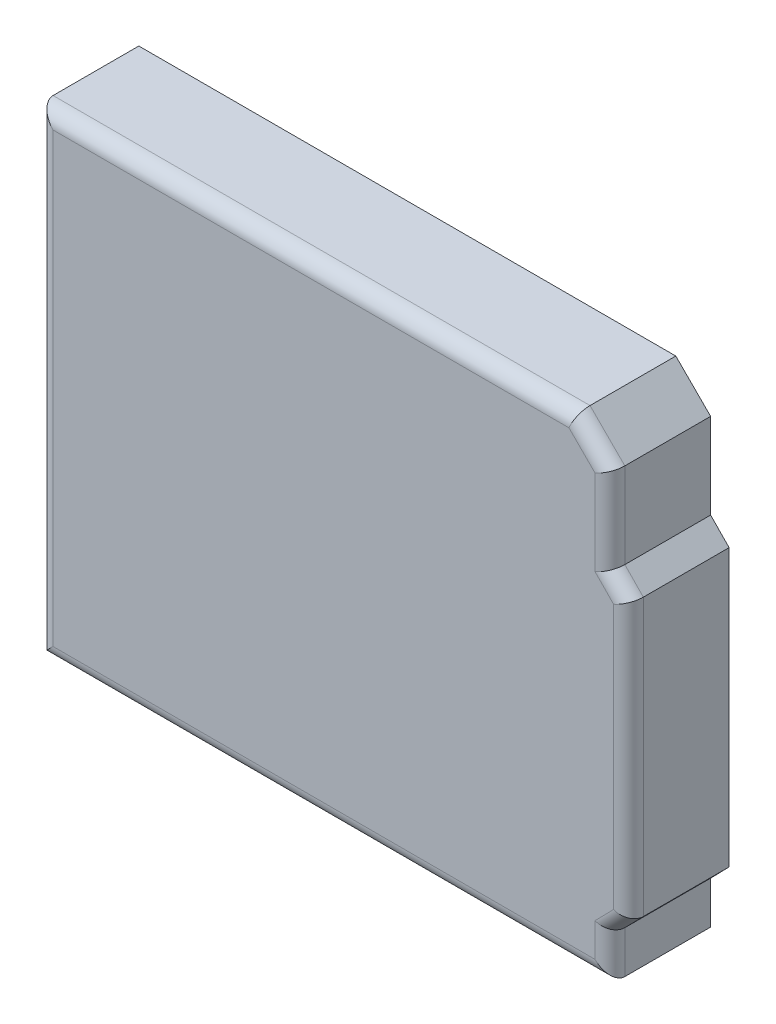
SolidWorks part; units mm, degrees
ref_plane "Front Plane" through (0, 0, 0) normal (0, 0, 1) x (1, 0, 0)
ref_plane "Top Plane" through (0, 0, 0) normal (0, 1, 0) x (1, 0, 0)
ref_plane "Right Plane" through (0, 0, 0) normal (1, 0, 0) x (0, 0, -1)
sketch "Sketch4" plane through (0, 0, 0) normal (0, 0, 1) x (1, 0, 0)
  line L25 (-58.7815, 16.139) -> (-58.7815, -3.121)
  line L26 (-58.7815, -3.121) -> (-54.0815, -3.121)
  line L27 (-54.0815, -3.121) -> (-54.0815, 16.139)
  line L28 (-54.0815, 16.139) -> (-58.7815, 16.139)
  line L29 (-54.0815, -12.7107) -> (-58.7815, -12.7107)
  line L30 (-58.7815, -12.7107) -> (-58.7815, -20.8795)
  line L31 (-58.7815, -20.8795) -> (17.8885, -20.8795)
  line L32 (17.8885, -20.8795) -> (17.8885, -15.1978)
  line L33 (17.8885, -15.1978) -> (20.3685, -12.6578)
  line L34 (20.3685, -12.6578) -> (20.3685, 24.4249)
  line L35 (20.3685, 24.4249) -> (17.8885, 26.9649)
  line L36 (17.8885, 26.9649) -> (17.8885, 38.4295)
  line L37 (17.8885, 38.4295) -> (13.2191, 43.099)
  line L38 (13.2191, 43.099) -> (-58.7815, 43.099)
  line L39 (-58.7815, 43.099) -> (-58.7815, 28.739)
  line L40 (-58.7815, 28.739) -> (-54.0815, 28.739)
  line L41 (-54.0815, 28.739) -> (-54.0815, 38.399)
  line L42 (-54.0815, 38.399) -> (13.1885, 38.399)
  line L43 (13.1885, 38.399) -> (13.1885, 25.0509)
  line L44 (13.1885, 25.0509) -> (15.6685, 22.5109)
  line L45 (15.6685, 22.5109) -> (15.6685, -10.7438)
  line L46 (15.6685, -10.7438) -> (13.1885, -13.2838)
  line L47 (13.1885, -13.2838) -> (13.1885, -16.1795)
  line L48 (13.1885, -16.1795) -> (-54.0815, -16.1795)
  line L49 (-54.0815, -16.1795) -> (-54.0815, -12.7107)
  line L51 (-58.7815, 28.739) -> (-54.0815, 28.739)
  line L52 (-58.7815, 28.739) -> (-58.7815, 16.139)
  line L53 (-58.7815, 16.139) -> (-54.0815, 16.139)
  line L54 (-54.0815, 28.739) -> (-54.0815, 16.139)
  line L55 (-58.7815, -3.121) -> (-54.0815, -3.121)
  line L56 (-58.7815, -3.121) -> (-58.7815, -12.7107)
  line L57 (-58.7815, -12.7107) -> (-54.0815, -12.7107)
  line L58 (-54.0815, -3.121) -> (-54.0815, -12.7107)
extrude "Boss-Extrude1" add sketch "Sketch4" along normal blind 13.5 contours L27 L58 L49 L48 L47 L46 L45 L44 L43 L42 L41 L54 | L48 L49 L29 L30 L31 L32 L33 L34 L35 L36 L37 L38 L39 L40 L41 L42 L43 L44 L45 L46 L47 | L54 L40 L52 L28 | L27 L28 L25 L26 | L58 L26 L56 L29 region at (-56.4315, 6.509, 0) region at (-56.4315, 22.439, 0) region at (-56.4315, -7.9158, 0) region at (-19.6238, 10.9864, 0) region at (-57.7637, 35.919, 0)
sketch "Sketch6" plane through (0, 0, 0) normal (0, 0, -1) x (-1, 0, 0)
  line L54 (53.7815, -15.8795) -> (53.7815, 38.099)
  line L55 (-12.8885, -15.8795) -> (53.7815, -15.8795)
  line L56 (-15.3685, -10.6216) -> (-12.8885, -13.1616)
  line L57 (-15.3685, 22.3887) -> (-15.3685, -10.6216)
  line L58 (-12.8885, 24.9287) -> (-15.3685, 22.3887)
  line L59 (-12.8885, 36.3585) -> (-12.8885, 24.9287)
  line L60 (53.7815, 38.099) -> (-11.148, 38.099)
  line L61 (53.7815, -15.8795) -> (53.7815, 38.099)
  line L62 (-12.8885, -15.8795) -> (53.7815, -15.8795)
  line L63 (-15.3685, -10.6216) -> (-12.8885, -13.1616)
  line L64 (-15.3685, 22.3887) -> (-15.3685, -10.6216)
  line L65 (-12.8885, 24.9287) -> (-15.3685, 22.3887)
  line L66 (-12.8885, 36.3585) -> (-12.8885, 24.9287)
  line L67 (53.7815, 38.099) -> (-11.148, 38.099)
  line L68 (-12.8885, -13.1616) -> (-12.8885, -15.8795)
  line L69 (-12.8885, -13.1616) -> (-12.8885, -15.8795)
  line L70 (-11.148, 38.099) -> (-12.8885, 36.3585)
  line L71 (-11.148, 38.099) -> (-12.8885, 36.3585)
  dimension "D1" = 5
extrude "Cut-Extrude1" cut sketch "Sketch6" against normal blind 8.5
fillet "Fillet2" radius 2 9 edges at (19.1285, 25.6949, 13.5) (17.8885, 32.6972, 13.5) (15.5538, 40.7643, 13.5) (-22.7812, 43.099, 13.5) (-58.7815, 11.1098, 13.5) (-20.4465, -20.8795, 13.5) (17.8885, -18.0386, 13.5) (19.1285, -13.9278, 13.5) (20.3685, 5.8835, 13.5)
